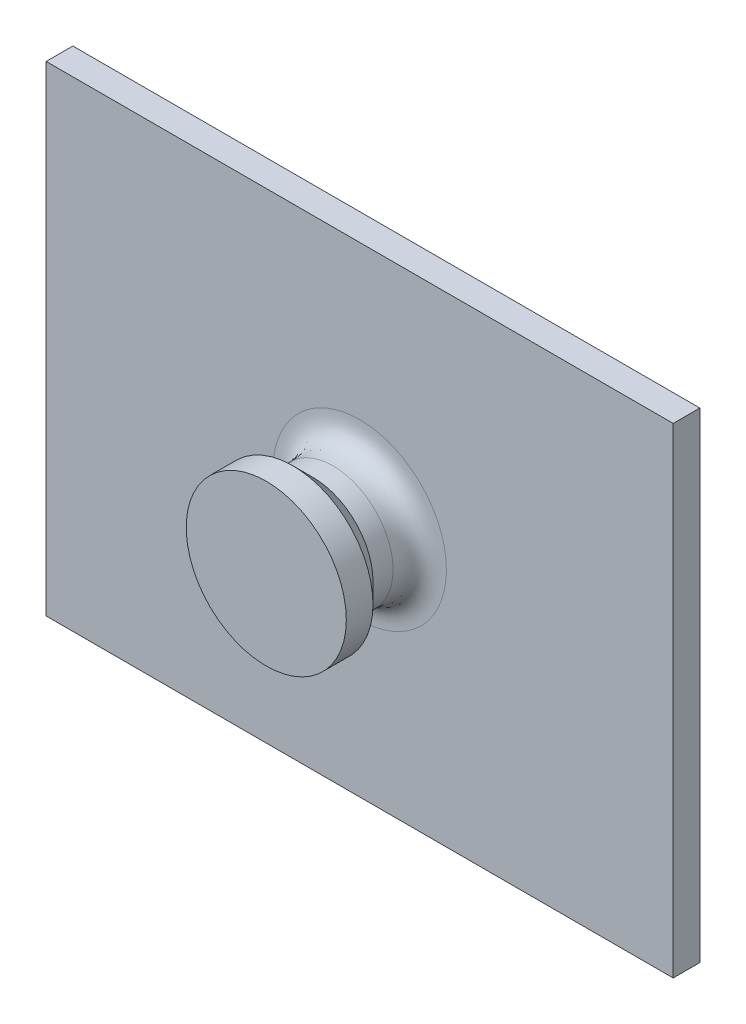
SolidWorks part; units mm, degrees
ref_plane "Front Plane" through (0, 0, 0) normal (0, 0, 1) x (1, 0, 0)
ref_plane "Top Plane" through (0, 0, 0) normal (0, 1, 0) x (1, 0, 0)
ref_plane "Right Plane" through (0, 0, 0) normal (1, 0, 0) x (0, 0, -1)
sketch "Sketch1" plane through (0, 0, 0) normal (0, 0, 1) x (1, 0, 0)
  line L1 (0, 10.3478) -> (47, 10.3478)
  line L2 (0, 10.3478) -> (0, 46.3478)
  line L3 (0, 46.3478) -> (47, 46.3478)
  line L4 (47, 10.3478) -> (47, 46.3478)
  dimension "D1" = 47
  dimension "D2" = 36
extrude "Boss-Extrude1" add sketch "Sketch1" along normal blind 2
sketch "Sketch2" plane through (0, 0, 2) normal (0, 0, 1) x (1, 0, 0)
  line L0 (0, 10.3478) -> (47, 10.3478) construction
  line L1 (47, 10.3478) -> (47, 46.3478) construction
  circle A0 centre (23.5, 28.3478) radius 4.5
  point P4 (23.5, 10.3478)
  point P7 (47, 28.3478)
  dimension "D1" = 9
extrude "Boss-Extrude2" add sketch "Sketch2" along normal blind 5
sketch "Sketch3" plane through (0, 0, 7) normal (0, 0, 1) x (1, 0, 0)
  circle A1 centre (23.5, 28.3478) radius 6
  circle A2 centre (23.5, 28.3478) radius 4.5
  circle A3 centre (23.5, 28.3478) radius 4.5 construction
  dimension "D1" = 0
  dimension "D2" = 12
extrude "Boss-Extrude3" add sketch "Sketch3" along normal blind 2
fillet "Fillet1" radius 2 1 edges at (28, 28.3478, 2) curvature continuous yes
chamfer "Chamfer1" distance 1.5 angle 45 1 edges at (28, 28.3478, 7)
